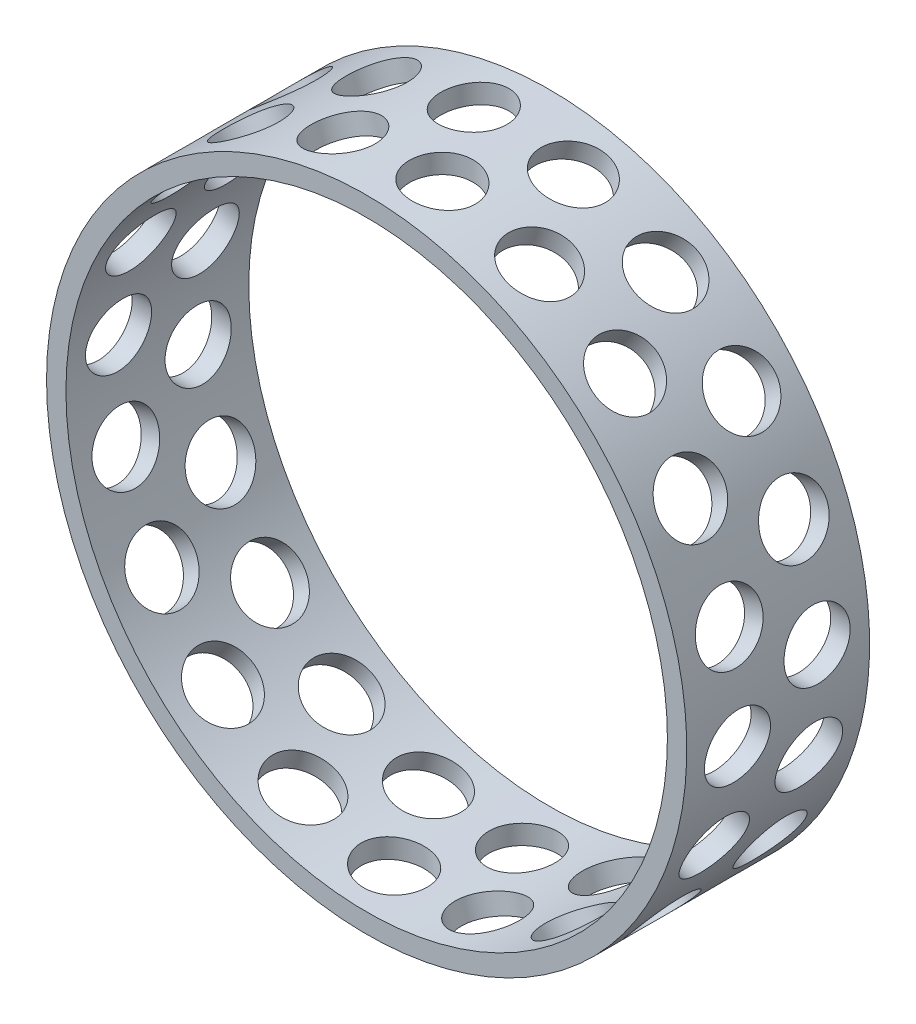
SolidWorks part; units mm, degrees
material "Plain Carbon Steel"
ref_plane "Front Plane" through (0, 0, 0) normal (0, 0, 1) x (1, 0, 0)
ref_plane "Top Plane" through (0, 0, 0) normal (0, 1, 0) x (1, 0, 0)
ref_plane "Right Plane" through (0, 0, 0) normal (1, 0, 0) x (0, 0, -1)
sketch "Sketch1" plane through (0, 0, 0) normal (1, 0, 0) x (0, 0, -1)
  line L0 (1, 82.55) -> (48.15, 82.55)
  line L1 (48.15, 82.55) -> (48.15, 77.55)
  line L2 (48.15, 77.55) -> (1, 77.55)
  line L3 (1, 77.55) -> (1, 82.55)
  dimension "D1" = 82.55
  dimension "D2" = 5
  dimension "D3" = 47.15
  dimension "D4" = 1
ref_axis "Axis1" through (0, 0, -50.5075) along (0, 0, 1)
revolve "Revolve1" add sketch "Sketch1" angle 360 about axis through (0, 0, -50.5075) along (0, 0, 1)
sketch "Sketch2" plane through (0, 0, 0) normal (1, 0, 0) x (0, 0, -1)
  line L0 (14.3098, 6.2149) -> (24.575, 0) construction
  line L1 (50.5075, 0) -> (-1.3575, 0) construction
  line L2 (24.575, 0) -> (34.8402, -6.2149) construction
  line L3 (1, 82.55) -> (1, -82.55) construction
  circle A0 centre (14.3098, 6.2149) radius 8.5
  circle A1 centre (34.8402, -6.2149) radius 8.5
  dimension "D1" = 17
  dimension "D2" = 12
  dimension "D3" = 23.575
extrude "Cut-Extrude1" cut sketch "Sketch2" against normal through all
pattern_circular "CirPattern1" count 20 over 360 about axis through (0, 0, -50.5075) along (0, 0, 1) of "Cut-Extrude1"
equation "\"TubeDiameter\" = 6.500in"
equation "\"D1@Sketch1\"=\"TubeDiameter\"/2"
